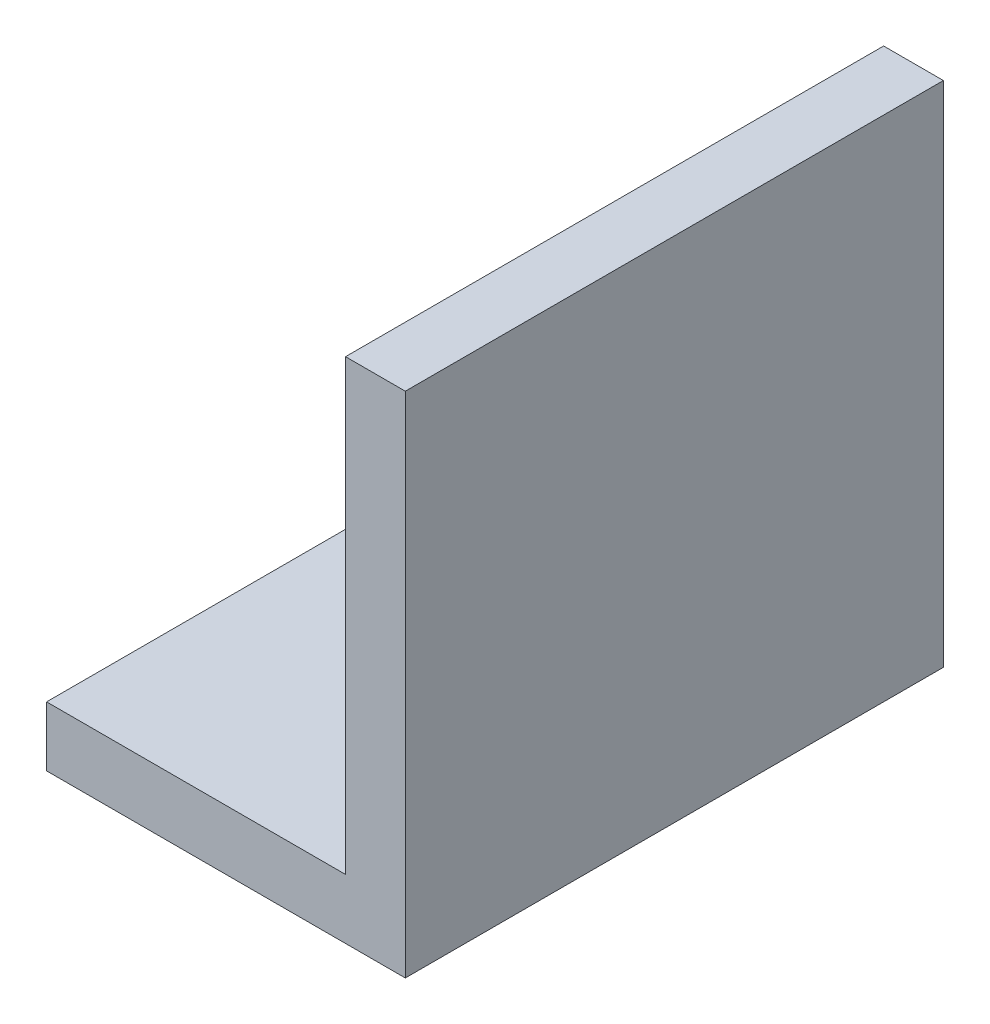
SolidWorks part; units mm, degrees
ref_plane "Спереди" through (0, 0, 0) normal (0, 0, 1) x (1, 0, 0)
ref_plane "Сверху" through (0, 0, 0) normal (0, 1, 0) x (1, 0, 0)
ref_plane "Справа" through (0, 0, 0) normal (1, 0, 0) x (0, 0, -1)
sketch "Эскиз1" plane through (0, 0, 0) normal (0, 0, 1) x (1, 0, 0)
  line L0 (0, 0) -> (-10, 0)
  line L1 (0, 0) -> (0, 15)
extrude "Вытянуть-Тонкостенный1" add sketch "Эскиз1" along normal blind 18 thin thin type one direction wall 2
